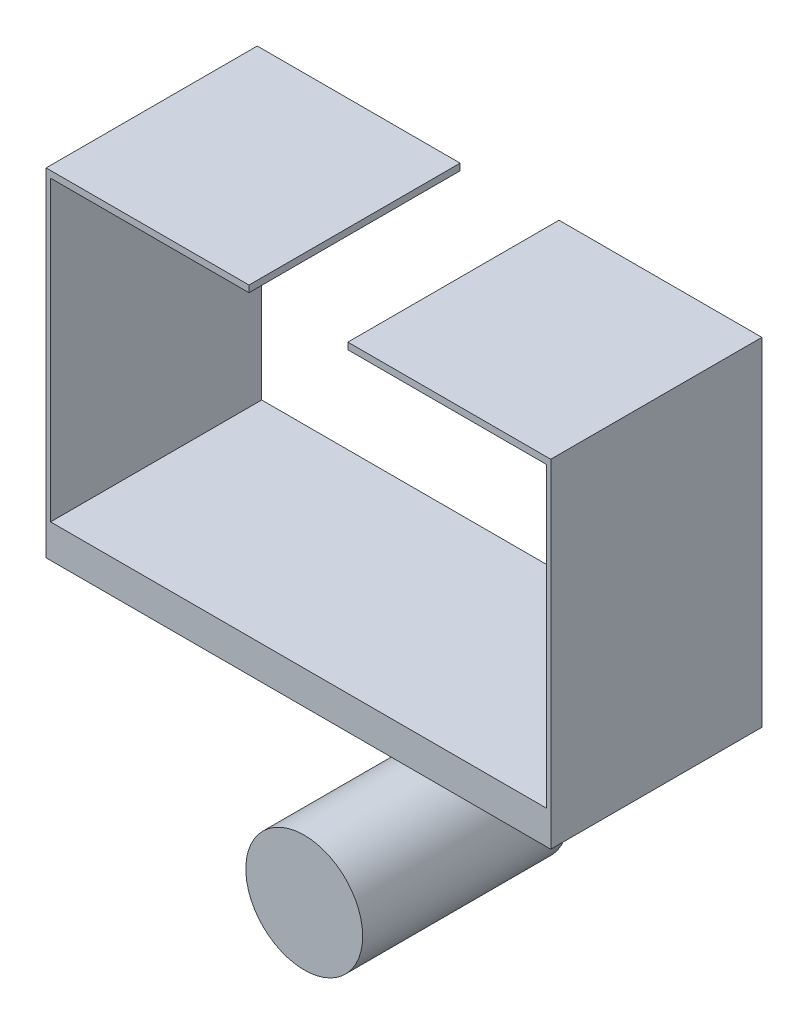
SolidWorks part; units mm, degrees
material "Ti-6Al-4VSolution treated and aged (SS)"
ref_plane "Front Plane" through (0, 0, 0) normal (0, 0, 1) x (1, 0, 0)
ref_plane "Top Plane" through (0, 0, 0) normal (0, 1, 0) x (1, 0, 0)
ref_plane "Right Plane" through (0, 0, 0) normal (1, 0, 0) x (0, 0, -1)
sketch "Sketch1" plane through (0, 0, 0) normal (0, 0, 1) x (1, 0, 0)
  circle A0 centre (0, 0) radius 7.4727
  dimension "D1" = 7.4727
extrude "Boss-Extrude1" add sketch "Sketch1" against normal blind 25.4 contours A0
sketch "Sketch2" plane through (0, 0, -25.4) normal (0, 0, -1) x (-1, 0, 0)
  line L0 (-7.4727, 0) -> (7.4727, 0)
  line L2 (-7.4727, 0) -> (7.4727, 0)
  line L3 (-7.4727, 0) -> (-7.4727, 22.4182)
  line L4 (-7.4727, 22.4182) -> (7.4727, 22.4182)
  line L5 (7.4727, 0) -> (7.4727, 22.4182)
  circle A0 centre (0, 0) radius 7.4727
  point P5 (0, 0)
  circle M2 centre (0, 0) radius 7.4727
  dimension "D1" = 14.9455
  dimension "D2" = 22.4182
extrude "Boss-Extrude2" add sketch "Sketch2" along normal blind 0.8634 contours L0 M2 | L0 M2 | L3 L2 L5 L4 region at (0, 3.1715, -25.4) region at (0, -3.1715, -25.4)
sketch "Sketch4" plane through (0, 0, -26.2634) normal (0, 0, -1) x (-1, 0, 0)
  line L0 (-7.4727, 22.4182) -> (7.4727, 22.4182) construction
  line L1 (-31.7043, 26.6881) -> (31.7043, 26.6881)
  line L2 (-31.7043, 26.6881) -> (-31.7043, 22.4182)
  line L3 (-31.7043, 22.4182) -> (31.7043, 22.4182)
  line L4 (31.7043, 26.6881) -> (31.7043, 22.4182)
  line L5 (-31.7043, 24.5532) -> (31.7043, 24.5532) construction
  line L6 (0, 24.5532) -> (0, 20.2833)
  point P8 (0, 0)
  point P12 (0, 22.4182)
  point P13 (0, 24.5532)
  point P14 (0, 0)
  dimension "D1" = 63.4086
  dimension "D2" = 4.2698
extrude "Boss-Extrude3" add sketch "Sketch4" against normal blind 27.0042 contours L1 L4 L3 L2
sketch "Sketch6" plane through (31.7043, 0, 0) normal (1, 0, 0) x (0, 0, -1)
  line L1 (-0.7409, 26.6881) -> (26.2634, 26.6881)
  line L2 (-0.7409, 26.6881) -> (-0.7409, 22.4182)
  line L3 (-0.7409, 22.4182) -> (26.2634, 22.4182)
  line L4 (26.2634, 26.6881) -> (26.2634, 22.4182)
extrude "Boss-Extrude4" add sketch "Sketch6" along normal blind 0.5689
sketch "Sketch7" plane through (0, 26.6881, 0) normal (0, 1, 0) x (1, 0, 0)
  line L0 (31.7043, -0.7409) -> (31.7043, 26.2634) construction
  line L1 (31.7043, 26.2634) -> (32.2732, 26.2634)
  line L2 (31.7043, 26.2634) -> (31.7043, -0.7409)
  line L3 (31.7043, -0.7409) -> (32.2732, -0.7409)
  line L4 (32.2732, 26.2634) -> (32.2732, -0.7409)
  line L5 (32.2732, 26.2634) -> (-31.7043, 26.2634) construction
extrude "Boss-Extrude5" add sketch "Sketch7" along normal blind 38.0746
sketch "Sketch8" plane through (0, 64.7627, 0) normal (0, 1, 0) x (1, 0, 0)
  line L1 (31.7043, 26.2634) -> (32.2732, 26.2634)
  line L2 (31.7043, 26.2634) -> (31.7043, -0.7409)
  line L3 (31.7043, -0.7409) -> (32.2732, -0.7409)
  line L4 (32.2732, 26.2634) -> (32.2732, -0.7409)
extrude "Boss-Extrude6" add sketch "Sketch8" along normal blind 0.8534
sketch "Sketch9" plane through (31.7043, 0, 0) normal (-1, 0, 0) x (0, 0, 1)
  line L0 (-26.2634, 64.7627) -> (0.7409, 64.7627) construction
  line L1 (-26.2634, 65.6161) -> (0.7409, 65.6161)
  line L2 (-26.2634, 65.6161) -> (-26.2634, 64.7627)
  line L3 (-26.2634, 64.7627) -> (0.7409, 64.7627)
  line L4 (0.7409, 65.6161) -> (0.7409, 64.7627)
  line L5 (0.7409, 65.6161) -> (0.7409, 26.6881) construction
extrude "Boss-Extrude7" add sketch "Sketch9" along normal blind 25.3797
mirror "Mirror1" about plane through (0, 0, 0) normal (1, 0, 0) of "Boss-Extrude7", "Boss-Extrude6", "Boss-Extrude5", "Boss-Extrude4"
equation "\"a\"= 0.498"
equation "\"b\"= 0.9992"
equation "\"c\"= 1.499"
equation "\"sf\"= 4"
equation "\"F\"= 600"
equation "\"E\"= 15199999.87"
equation "\"delt_max\"= 0.005"
equation "\"stress_y\"= 120000"
equation "\"L1\"= 1"
equation "\"W\"= 2 * \"F\""
equation "\"stress\"= \"stress_y\" / \"sf\""
equation "\"delt\"= \"delt_max\" / \"sf\""
equation "\"A1\"= \"F\" / \"stress\""
equation "\"Z\"= \"W\" / ( 2 * \"stress\" )"
equation "\"r1\"= ( ( 4 * \"Z\" ) / PI ) ^ ( 1 / 3 )"
equation "\"w1\"= 2 * \"r1\""
equation "\"t1\"= \"A1\" / \"w1\""
equation "\"base1\"= \"t1\" + \"L1\""
equation "\"h1\"= ( \"A1\" * 2 ) / \"base1\""
equation "\"w2\"= \"A1\" / \"c\""
equation "\"h2\"= \"A1\" / \"b\""
equation "\"I1\"= ( 5 * \"W\" * ( \"L1\" ^ 3 ) ) / ( 384 * \"E\" * \"delt\" )"
equation "\"r2\"= ( ( \"I1\" * 4 ) / PI ) ^ ( 1 / 4 )"
equation "\"L2\"= 4 * \"r2\""
equation "\"w3\"= 2 * \"r2\""
equation "\"A2\"= ( \"F\" * \"L2\" ) / ( \"E\" * \"delt\" )' "
equation "\"t2\"= \"A2\" / \"w3\"' "
equation "\"base2\"= \"L1\" + \"t2\""
equation "\"L3\"= \"a\" + ( 2 * \"b\" )' "
equation "\"I2\"= ( 5 * \"W\" * ( \"base2\" ^ 3 ) ) / ( 384 * \"E\" * \"delt\" )"
equation "\"h3\"= ( ( 12 * \"I2\" ) / \"L3\" ) ^ ( 1 / 3 )"
equation "\"A3\"= ( \"F\" * \"base2\" ) / ( \"E\" * \"delt\" )"
equation "\"w4\"= \"A3\" / \"c\""
equation "\"h4\"= \"A3\" / \"b\""
equation "\"D1@Sketch1\"=\"r1\""
equation "\"D1@Boss-Extrude1\"=\"L1\""
equation "\"D1@Sketch2\"=\"r1\"*2"
equation "\"D1@Boss-Extrude2\"=\"t1\""
equation "\"D2@Sketch2\"=3*\"r1\""
equation "\"D1@Sketch4\"=\"L3\""
equation "\"D2@Sketch4\"=\"h3\""
equation "\"D1@Boss-Extrude3\"=\"base2\""
equation "\"D1@Boss-Extrude4\"=\"w4\""
equation "\"D1@Boss-Extrude5\"=\"c\""
equation "\"D1@Boss-Extrude6\"=\"h4\""
equation "\"D1@Boss-Extrude7\"=\"b\""
